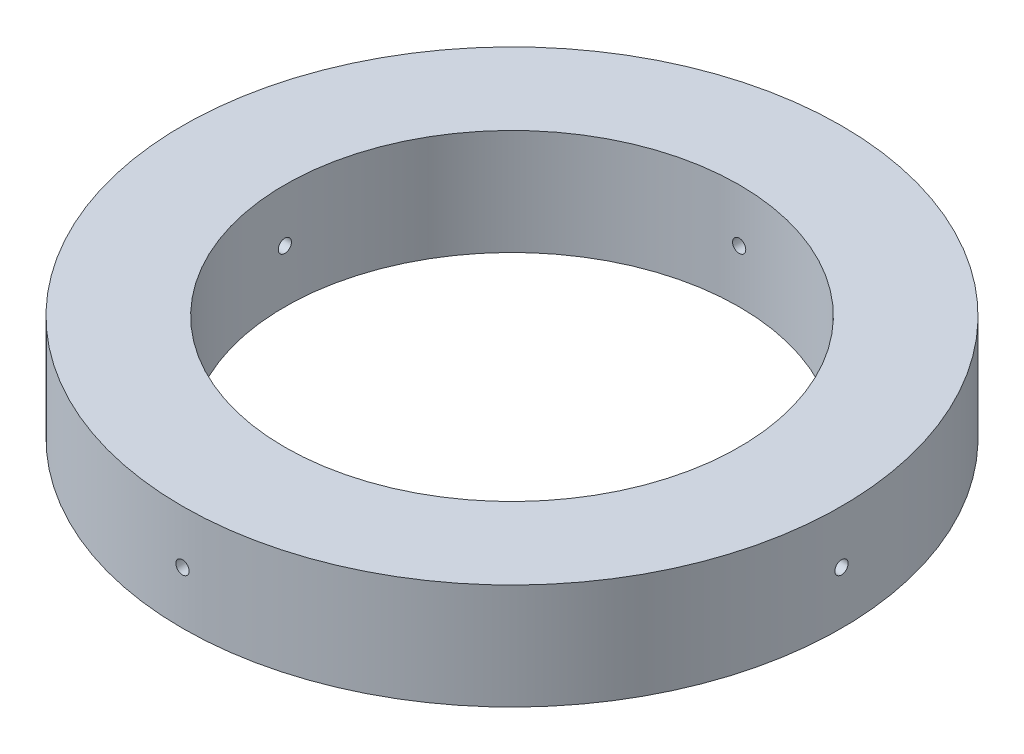
SolidWorks part; units mm, degrees
ref_plane "Front Plane" through (0, 0, 0) normal (0, 0, 1) x (1, 0, 0)
ref_plane "Top Plane" through (0, 0, 0) normal (0, 1, 0) x (1, 0, 0)
ref_plane "Right Plane" through (0, 0, 0) normal (1, 0, 0) x (0, 0, -1)
sketch "Croquis1" plane through (0, 0, 0) normal (0, 1, 0) x (1, 0, 0)
  circle A0 centre (0, 0) radius 43
  circle A1 centre (0, 0) radius 62.36
  dimension "D1" = 86
  dimension "D2" = 124.72
extrude "Saliente-Extruir1" add sketch "Croquis1" along normal blind 20
sketch "Croquis2" plane through (0, 0, 0) normal (0, 0, 1) x (1, 0, 0)
  circle A0 centre (0, 10) radius 1.25
  dimension "D2" = 2.5
  dimension "D1" = 10
extrude "Cortar-Extruir1" cut sketch "Croquis2" against normal up to surface (62.3475 mm away) up to face at (0, 20, 62.36)
pattern_circular "MatrizC1" count 4 over 360 about axis through (0, 20, 0) along (0, 1, 0) of "Cortar-Extruir1"
equation "\"D2@Croquis1\"=84.72+20*2"
